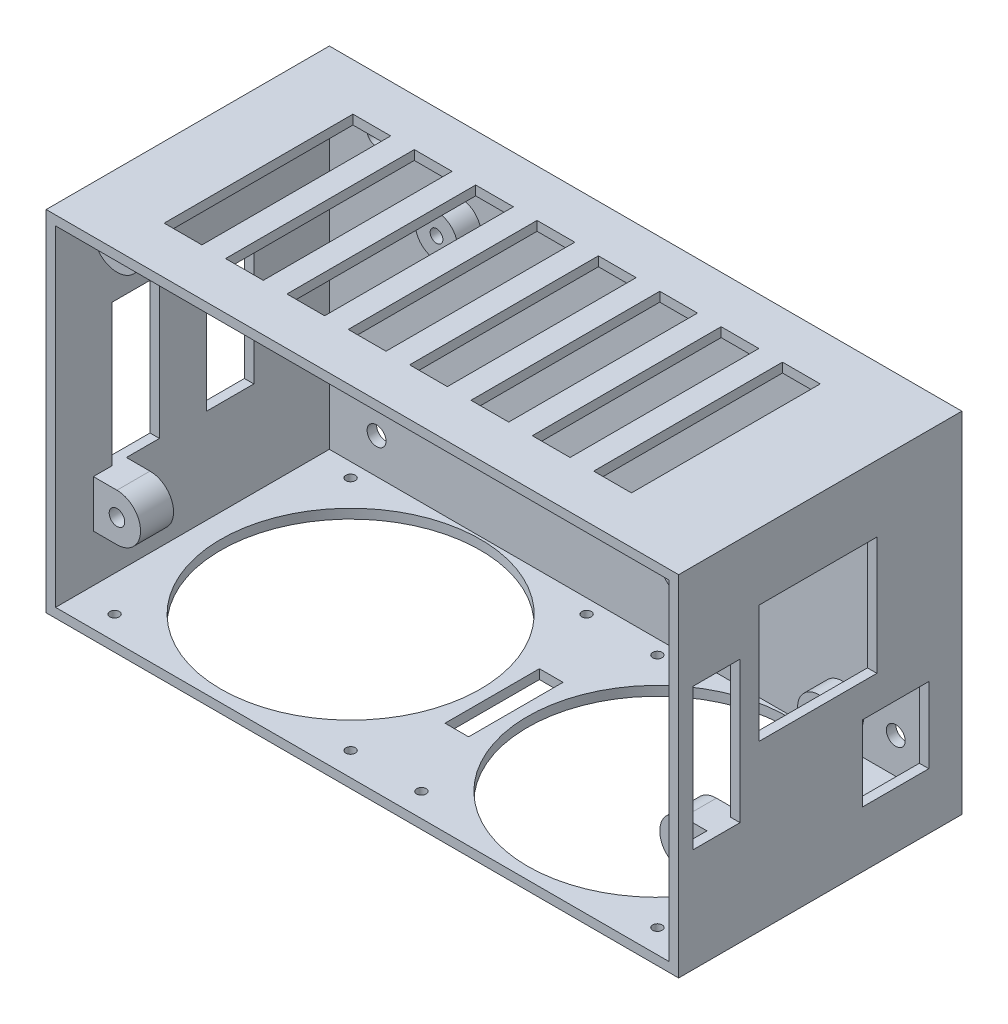
SolidWorks part; units mm, degrees
material "ABS"
ref_plane "Plano frontal" through (0, 0, 0) normal (0, 0, 1) x (1, 0, 0)
ref_plane "Plano superior" through (0, 0, 0) normal (0, 1, 0) x (1, 0, 0)
ref_plane "Plano direito" through (0, 0, 0) normal (1, 0, 0) x (0, 0, -1)
sketch "Esboço1" plane through (0, 0, 0) normal (0, 0, 1) x (1, 0, 0)
  line L0 (-67, 37) -> (67, 37)
  line L1 (-65, 35) -> (65, 35)
  line L2 (-65, 35) -> (-65, -35)
  line L3 (-65, -35) -> (65, -35)
  line L4 (65, 35) -> (65, -35)
  line L5 (-65, 35) -> (65, -35) construction
  line L6 (-65, -35) -> (65, 35) construction
  line L7 (67, 37) -> (67, -37)
  line L8 (-67, -37) -> (67, -37)
  line L9 (-67, 37) -> (-67, -37)
  point P0 (0, 0)
  dimension "D2" = 130
  dimension "D3" = 70
  dimension "D1" = 2
extrude "Ressalto-extrusão1" add sketch "Esboço1" along normal blind 60
sketch "Esboço2" plane through (0, 0, 0) normal (0, 0, -1) x (-1, 0, 0)
  line L0 (-67, -37) -> (-67, 37) construction
  line L1 (67, -37) -> (-67, -37) construction
  line L2 (-67, 37) -> (67, 37) construction
  line L3 (67, 37) -> (67, -37) construction
  line L4 (-67, -37) -> (-67, 37)
  line L5 (67, -37) -> (-67, -37)
  line L6 (-67, 37) -> (67, 37)
  line L7 (67, 37) -> (67, -37)
  line L8 (55, 27.5) -> (-55, 27.5) construction
  line L9 (-55, 27.5) -> (-55, -27.5) construction
  line L10 (-55, -27.5) -> (55, -27.5) construction
  line L11 (55, -27.5) -> (55, 27.5) construction
  circle A0 centre (-55, -27.5) radius 2
  circle A1 centre (55, -27.5) radius 2
  circle A2 centre (55, 27.5) radius 2
  circle A3 centre (-55, 27.5) radius 2
  point P12 (0, 27.5)
  point P13 (0, 37)
  point P14 (-55, 0)
  point P15 (-67, 0)
  dimension "D1" = 4
  dimension "D2" = 110
  dimension "D3" = 55
extrude "Ressalto-extrusão2" add sketch "Esboço2" against normal blind 2
sketch "Esboço3" plane through (67, 0, 0) normal (1, 0, 0) x (0, 0, -1)
  line L0 (-60, -37) -> (0, -37) construction
  line L1 (-43, 22.9) -> (-18, 22.9)
  line L2 (-43, 22.9) -> (-43, -2.1)
  line L3 (-43, -2.1) -> (-18, -2.1)
  line L4 (-18, 22.9) -> (-18, -2.1)
  line L5 (-21, -9.1) -> (-7, -9.1)
  line L6 (-21, -9.1) -> (-21, -25.1)
  line L7 (-21, -25.1) -> (-7, -25.1)
  line L8 (-7, -9.1) -> (-7, -25.1)
  line L11 (-60, -37) -> (-60, 37) construction
  line L12 (-57, 15) -> (-47, 15)
  line L13 (-57, 15) -> (-57, -15)
  line L14 (-57, -15) -> (-47, -15)
  line L15 (-47, 15) -> (-47, -15)
  line L16 (-57, 15) -> (-47, -15) construction
  line L17 (-57, -15) -> (-47, 15) construction
  line L18 (0, -37) -> (0, 37) construction
  point P14 (-52, 0)
  point P23 (-60, 0)
  dimension "D1" = 16
  dimension "D2" = 14
  dimension "D3" = 11.9
  dimension "D4" = 7
  dimension "D5" = 25
  dimension "D6" = 25
  dimension "D7" = 7
  dimension "D8" = 18
  dimension "D9" = 8
  dimension "D10" = 30
  dimension "D11" = 10
extrude "USB + fonte" cut sketch "Esboço3" against normal blind 10
sketch "Esboço6" plane through (0, -37, 0) normal (0, -1, 0) x (1, 0, 0)
  line L1 (-52, 50) -> (-44, 50)
  line L2 (-52, 50) -> (-52, 10)
  line L3 (-52, 10) -> (-44, 10)
  line L4 (-44, 50) -> (-44, 10)
  line L5 (-67, 60) -> (-67, 0) construction
  line L6 (-39, 50) -> (-31, 50)
  line L7 (-39, 50) -> (-39, 10)
  line L8 (-39, 10) -> (-31, 10)
  line L9 (-31, 50) -> (-31, 10)
  line L10 (-26, 50) -> (-18, 50)
  line L11 (-26, 50) -> (-26, 10)
  line L12 (-26, 10) -> (-18, 10)
  line L13 (-18, 50) -> (-18, 10)
  line L14 (-13, 50) -> (-5, 50)
  line L15 (-13, 50) -> (-13, 10)
  line L16 (-13, 10) -> (-5, 10)
  line L17 (-5, 50) -> (-5, 10)
  line L18 (0, 50) -> (8, 50)
  line L19 (0, 50) -> (0, 10)
  line L20 (0, 10) -> (8, 10)
  line L21 (8, 50) -> (8, 10)
  line L22 (13, 50) -> (21, 50)
  line L23 (13, 50) -> (13, 10)
  line L24 (13, 10) -> (21, 10)
  line L25 (21, 50) -> (21, 10)
  line L26 (26, 50) -> (34, 50)
  line L27 (26, 50) -> (26, 10)
  line L28 (26, 10) -> (34, 10)
  line L29 (34, 50) -> (34, 10)
  line L30 (39, 50) -> (47, 50)
  line L31 (39, 50) -> (39, 10)
  line L32 (39, 10) -> (47, 10)
  line L33 (47, 50) -> (47, 10)
  line L34 (67, 60) -> (67, 0) construction
  point P4 (-52, 30)
  point P37 (67, 30)
  dimension "D1" = 8
  dimension "D2" = 40
  dimension "D4" = 15
  dimension "D5" = 8
extrude "saida de ar" cut sketch "Esboço6" against normal through all from offset 20 offset against normal yes
sketch "Esboço7" plane through (-67, 0, 0) normal (-1, 0, 0) x (0, 0, 1)
  line L1 (48, 15) -> (38, 15)
  line L2 (48, 15) -> (48, -15)
  line L3 (48, -15) -> (38, -15)
  line L4 (38, 15) -> (38, -15)
  line L5 (48, 15) -> (38, -15) construction
  line L6 (48, -15) -> (38, 15) construction
  line L7 (28, 15) -> (18, 15)
  line L8 (28, 15) -> (28, -15)
  line L9 (28, -15) -> (18, -15)
  line L10 (18, 15) -> (18, -15)
  line L11 (28, 15) -> (18, -15) construction
  line L12 (28, -15) -> (18, 15) construction
  line L13 (0, 37) -> (0, -37) construction
  point P0 (43, 0)
  point P5 (23, 0)
  dimension "D1" = 10
  dimension "D2" = 30
  dimension "D3" = 10
  dimension "D4" = 18
extrude "display" cut sketch "Esboço7" against normal blind 12
sketch "Esboço8" plane through (0, 0, 2) normal (0, 0, -1) x (-1, 0, 0)
  line L0 (-65, -35) -> (-65, 35) construction
  line L1 (-65, 35) -> (65, 35) construction
  circle A0 centre (-43.7, -27.67) radius 4.5
  circle A1 centre (-43.7, -27.67) radius 1.35
  circle A2 centre (37.3, 20.5) radius 4.5
  circle A3 centre (37.3, 20.5) radius 1.35
  circle A4 centre (-45, 20.5) radius 1.35
  circle A5 centre (-45, 20.5) radius 1.35
  circle A6 centre (-45, 20.5) radius 4.5
  dimension "D1" = 9
  dimension "D2" = 2.7
  dimension "D3" = 82.3
  dimension "D4" = 48.17
  dimension "D5" = 1.3
  dimension "D6" = 20
  dimension "D7" = 14.5
extrude "Ressalto-extrusão3" add sketch "Esboço8" against normal blind 5 contours A2 A3 | A6 A4 | A0 A1 region at (48.0727, -27.67, 2) region at (-32.9273, 20.5, 2) region at (49.3727, 20.5, 2)
extrude "Corte-extrusão4" cut sketch "Esboço8<3>" along normal through all contours A4 | A3 | A1
sketch "Esboço8<3>" plane through (0, 0, 2) normal (0, 0, -1) x (-1, 0, 0) same geometry as "Esboço8"
sketch "Esboço9" plane through (0, 0, 2) normal (0, 0, 1) x (1, 0, 0)
  circle A0 centre (45, 20.5) radius 3
  circle A1 centre (43.7, -27.67) radius 3
  circle A2 centre (-37.3, 20.5) radius 3
  circle A3 centre (43.7, -27.67) radius 1.35 construction
  dimension "D1" = 6
extrude "Corte-extrusão5" cut sketch "Esboço9" along normal offset from surface 3 and the other way blind 10 up to face at (-32.8, 20.5, 7)
sketch "Esboço10" plane through (0, 37, 0) normal (0, 1, 0) x (1, 0, 0)
  line L0 (32.5, -30) -> (-32.5, -30) construction
  line L1 (67, -60) -> (-67, -60) construction
  line L2 (67, -60) -> (67, 0) construction
  line L4 (7.5, -5) -> (57.5, -5) construction
  line L5 (7.5, -5) -> (7.5, -55) construction
  line L6 (7.5, -55) -> (57.5, -55) construction
  line L7 (57.5, -5) -> (57.5, -55) construction
  line L8 (7.5, -5) -> (57.5, -55) construction
  line L9 (7.5, -55) -> (57.5, -5) construction
  line L10 (-57.5, -5) -> (-7.5, -5) construction
  line L11 (-57.5, -5) -> (-57.5, -55) construction
  line L12 (-57.5, -55) -> (-7.5, -55) construction
  line L13 (-7.5, -5) -> (-7.5, -55) construction
  line L14 (-57.5, -5) -> (-7.5, -55) construction
  line L15 (-57.5, -55) -> (-7.5, -5) construction
  line L16 (-2.5, -20) -> (2.5, -20)
  line L17 (-2.5, -20) -> (-2.5, -40)
  line L18 (-2.5, -40) -> (2.5, -40)
  line L19 (2.5, -20) -> (2.5, -40)
  line L20 (-2.5, -20) -> (2.5, -40) construction
  line L21 (-2.5, -40) -> (2.5, -20) construction
  circle A0 centre (32.5, -30) radius 27.5
  circle A1 centre (-32.5, -30) radius 27.5
  circle A2 centre (-57.5, -55) radius 1
  circle A3 centre (-7.5, -55) radius 1
  circle A4 centre (7.5, -55) radius 1
  circle A5 centre (57.5, -55) radius 1
  circle A6 centre (57.5, -5) radius 1
  circle A7 centre (7.5, -5) radius 1
  circle A8 centre (-7.5, -5) radius 1
  circle A9 centre (-57.5, -5) radius 1
  point P4 (0, -30)
  point P7 (0, -60)
  point P10 (67, -30)
  point P27 (0, -30)
  dimension "D2" = 55
  dimension "D3" = 2
  dimension "D1" = 65
  dimension "D4" = 50
  dimension "D5" = 5
  dimension "D6" = 20
extrude "cooler" cut sketch "Esboço10" against normal through all from vertex starting at point (-65, -35, 2)
sketch "Esboço11" plane through (0, 0, 60) normal (0, 0, 1) x (1, 0, 0)
  line L0 (-65, 35) -> (-65, -35) construction
  line L1 (65, -25) -> (60, -25)
  line L2 (65, -25) -> (65, -15)
  line L3 (65, 35) -> (60, 35)
  line L4 (-65, -25) -> (-65, -15)
  line L5 (65, -25) -> (-65, 35) construction
  line L6 (65, 35) -> (-65, -25) construction
  line L7 (-67, 37) -> (-67, -37) construction
  line L8 (60, 30) -> (-60, 30) construction
  line L9 (60, 30) -> (60, -20) construction
  line L10 (60, -20) -> (-60, -20) construction
  line L11 (-60, 30) -> (-60, -20) construction
  line L12 (60, 30) -> (-60, -20) construction
  line L13 (60, -20) -> (-60, 30) construction
  line L14 (67, 37) -> (-67, 37) construction
  line L15 (-60, 35) -> (-65, 35)
  line L16 (-65, 30) -> (-65, 35)
  line L17 (65, 30) -> (65, 35)
  line L18 (-60, -25) -> (-65, -25)
  line L19 (65, -35) -> (65, 35) construction
  line L20 (-60, -15) -> (-65, -15)
  line L21 (-65, 35) -> (-65, -35) construction
  line L22 (60, -15) -> (65, -15)
  line L23 (65, -35) -> (65, 35) construction
  arc A0 (-65, 30) -> (-60, 35) centre (-60, 30) ccw
  circle A1 centre (-60, 30) radius 1.65
  arc A2 (60, 35) -> (65, 30) centre (60, 30) ccw
  circle A3 centre (60, 30) radius 1.65
  circle A5 centre (60, -20) radius 1.65
  arc A6 (-60, -25) -> (-60, -15) centre (-60, -20) ccw
  circle A7 centre (-60, -20) radius 1.65
  arc A8 (60, -15) -> (60, -25) centre (60, -20) ccw
  point P0 (0, 0)
  point P10 (0, 0)
  dimension "D3" = 3.3
  dimension "D1" = 7
  dimension "D2" = 7
  dimension "D4" = 120
  dimension "D5" = 50
extrude "Ressalto-extrusão4" add sketch "Esboço11" against normal blind 7 from offset 8 offset against normal yes
equation "\"D2@Esboço11\"=\"D1@Esboço11\""
